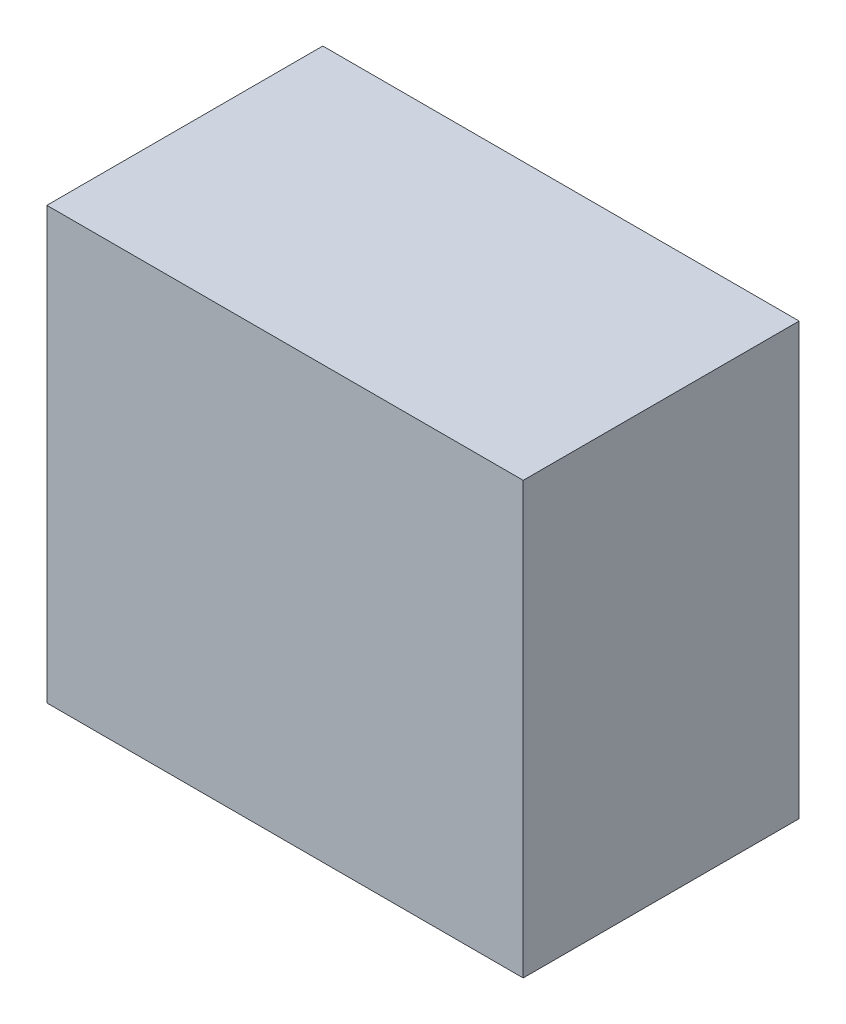
SolidWorks part; units mm, degrees
material "1060 Alloy"
ref_plane "Front" through (0, 0, 0) normal (0, 0, 1) x (1, 0, 0)
ref_plane "Top" through (0, 0, 0) normal (0, 1, 0) x (1, 0, 0)
ref_plane "Right" through (0, 0, 0) normal (1, 0, 0) x (0, 0, -1)
sketch "Sketch3" plane through (0, 0, 0) normal (0, 0, 1) x (1, 0, 0)
  line L0 (-0.127, -6.35) -> (30.1755, -6.35)
  line L1 (0, 0) -> (21.9242, 0)
  line L2 (0, 0) -> (0, -19.8376)
  line L3 (0, -19.8376) -> (21.9242, -19.8376)
  line L4 (21.9242, 0) -> (21.9242, -19.8376)
  line L5 (15.5742, -19.8376) -> (15.5742, 0) construction
  line L6 (15.5742, -6.35) -> (8.0621, -19.3614) construction
  line L15 (12.5496, -11.5887) -> (15.5742, -13.335) construction
  circle A0 centre (15.5742, -6.35) radius 6.0492 construction
  point P14 (0, -6.35)
  point P17 (9.525, -6.35)
  point P20 (7.7871, -19.8376)
  dimension "D2" = 6.35
  dimension "D6" = 3.4925
  dimension "D3" = 60
  dimension "D1" = 9.525
  dimension "D4" = 9.525
  dimension "D5" = 6.35
extrude "Boss-Extrude1" add sketch "Sketch3" along normal mid plane 12.7
sketch "Sketch4" plane through (0, 0, 0) normal (-1, 0, 0) x (0, 0, 1)
  circle A0 centre (0, -6.35) radius 3.175
  dimension "D1" = 6.35
extrude "Cut-Extrude1" cut sketch "Sketch4" against normal blind 9.525
ref_plane "Plane1" through (7.7871, -19.8376, 0) normal (-0.5, -0.866, 0) x (-0.866, 0.5, 0)
ref_plane "Mirror Plane" through (15.5742, 0, 0) normal (-1, 0, 0) x (0, 0, 1)
sketch "Sketch5" plane through (7.7871, -19.8376, 0) normal (-0.5, -0.866, 0) x (-0.866, 0.5, 0)
  circle A0 centre (0, 0) radius 3.175
  dimension "D1" = 6.35
extrude "Cut-Extrude5" cut sketch "Sketch5" against normal blind 9.525 and the other way up to next
sketch "Sketch6" plane through (0, 0, -6.35) normal (0, 0, -1) x (-1, 0, 0)
  circle A0 centre (-15.5742, -6.35) radius 3.175
  dimension "D1" = 6.35
extrude "Cut-Extrude6" cut sketch "Sketch6" against normal blind 9.525
equation "\"truss_member_od\" = .25in"
equation "\"truss_member_id\" = 0in"
equation "\"truss_member_L1\" = 2.75in"
equation "\"connector_hole_depth\" = .375in"
equation "\"D1@Boss-Extrude1\"=\"truss_member_od\"*2"
equation "\"D6@Sketch3\"=\"truss_member_od\"/2*1.1"
equation "\"D1@Sketch4\"=\"truss_member_od\""
equation "\"D1@Cut-Extrude1\"=\"connector_hole_depth\""
equation "\"D1@Sketch3\"=\"connector_hole_depth\""
equation "\"D4@Sketch3\"=\"connector_hole_depth\""
equation "\"D1@Sketch5\"=\"truss_member_od\""
equation "\"D1@Cut-Extrude5\"=\"connector_hole_depth\""
equation "\"D1@Cut-Extrude6\"=\"connector_hole_depth\""
equation "\"D1@Sketch6\"=\"truss_member_od\""
equation "\"D5@Sketch3\"=\"truss_member_od\""
